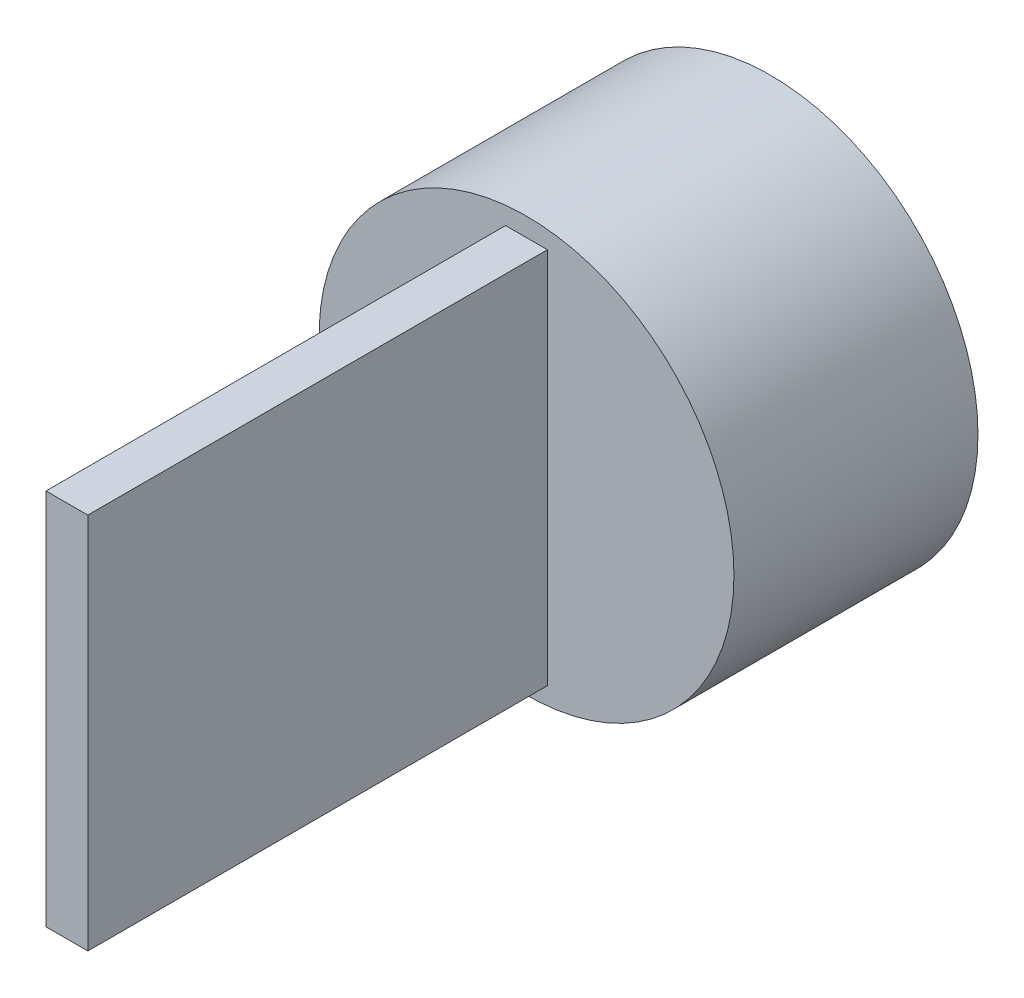
SolidWorks part; units mm, degrees
ref_plane "Ebene vorne" through (0, 0, 0) normal (0, 0, 1) x (1, 0, 0)
ref_plane "Ebene oben" through (0, 0, 0) normal (0, 1, 0) x (1, 0, 0)
ref_plane "Ebene rechts" through (0, 0, 0) normal (1, 0, 0) x (0, 0, -1)
sketch "Skizze1" plane through (0, 0, 0) normal (0, 0, 1) x (1, 0, 0)
  circle A0 centre (0, 0) radius 51
  dimension "D1" = 102
extrude "Aufsatz-Linear austragen1" add sketch "Skizze1" along normal blind 60
sketch "Skizze2" plane through (0, 0, 60) normal (0, 0, 1) x (1, 0, 0)
  line L1 (5.1416, 46.4093) -> (-5.1416, 46.4093)
  line L2 (5.1416, 46.4093) -> (5.1416, -46.4093)
  line L3 (5.1416, -46.4093) -> (-5.1416, -46.4093)
  line L4 (-5.1416, 46.4093) -> (-5.1416, -46.4093)
  line L5 (5.1416, 46.4093) -> (-5.1416, -46.4093) construction
  line L6 (5.1416, -46.4093) -> (-5.1416, 46.4093) construction
  point P0 (0, 0)
extrude "Aufsatz-Linear austragen2" add sketch "Skizze2" along normal blind 113
